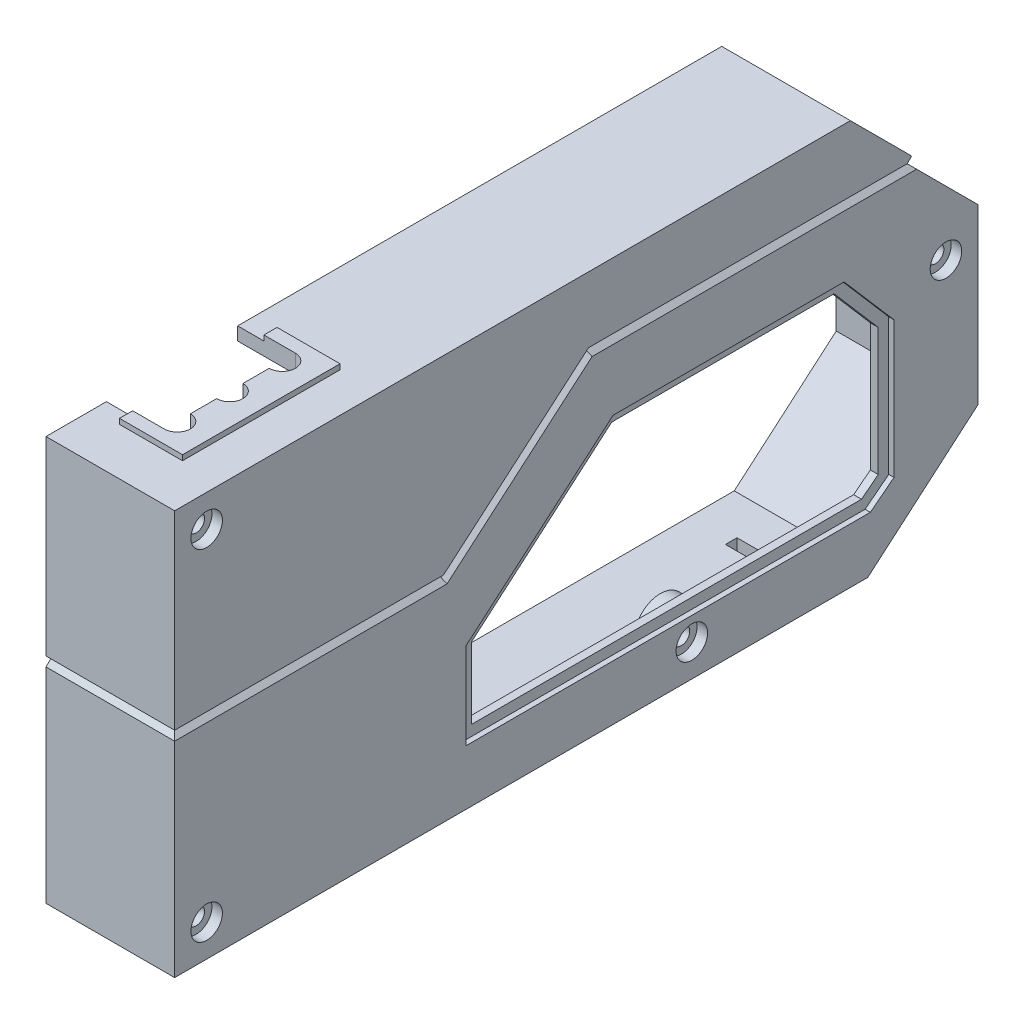
SolidWorks part; units mm, degrees
ref_plane "Front Plane" through (0, 0, 0) normal (0, 0, 1) x (1, 0, 0)
ref_plane "Top Plane" through (0, 0, 0) normal (0, 1, 0) x (1, 0, 0)
ref_plane "Right Plane" through (0, 0, 0) normal (1, 0, 0) x (0, 0, -1)
sketch "Sketch1" plane through (0, 0, 0) normal (1, 0, 0) x (0, 0, -1)
  line L0 (0, 0) -> (0, 77)
  line L1 (0, 77) -> (127, 77)
  line L2 (127, 77) -> (153, 51)
  line L3 (153, 51) -> (153, 18)
  line L4 (153, 18) -> (132, 0)
  line L5 (132, 0) -> (0, 0)
  dimension "D1" = 132
  dimension "D2" = 77
  dimension "D3" = 26
  dimension "D4" = 26
  dimension "D5" = 153
  dimension "D6" = 18
extrude "Base" add sketch "Sketch1" along normal blind 2.5
sketch "Sketch11" plane through (0, 0, 0) normal (-1, 0, 0) x (0, 0, 1)
  line L12 (-131.0752, 2.5) -> (-2.5, 2.5)
  line L13 (-2.5, 2.5) -> (-2.5, 74.5)
  line L14 (-2.5, 74.5) -> (-125.9645, 74.5)
  line L15 (-125.9645, 74.5) -> (-150.5, 49.9645)
  line L16 (-150.5, 49.9645) -> (-150.5, 19.1498)
  line L17 (-150.5, 19.1498) -> (-131.0752, 2.5)
  line L18 (-131.0752, 2.5) -> (-2.5, 2.5)
  line L19 (-2.5, 2.5) -> (-2.5, 74.5)
  line L20 (-2.5, 74.5) -> (-125.9645, 74.5)
  line L21 (-125.9645, 74.5) -> (-150.5, 49.9645)
  line L22 (-150.5, 49.9645) -> (-150.5, 19.1498)
  line L23 (-150.5, 19.1498) -> (-131.0752, 2.5)
  line M7 (-132, 0) -> (0, 0)
  line M8 (0, 0) -> (0, 77)
  line M9 (0, 77) -> (-127, 77)
  line M10 (-127, 77) -> (-153, 51)
  line M11 (-153, 51) -> (-153, 18)
  line M12 (-153, 18) -> (-132, 0)
  dimension "D1" = 2.5
extrude "Boss-Extrude6" add sketch "Sketch11" along normal blind 22 contours L23 L22 L21 L20 L19 L18 M12 M7 M8 M9 M10 M11 region at (0, 10.3005, -141.3853)
ref_plane "Middle" through (-11, 0, 0) normal (1, 0, 0) x (0, 0, -1)
sketch "Sketch17" plane through (0, 77, 0) normal (0, 1, 0) x (1, 0, 0)
  line L5 (-11, -42.35) -> (-11, 42.35) construction
  line L6 (-5, 39) -> (-17, 39)
  line L7 (-5, 39) -> (-5, 9)
  line L8 (-5, 9) -> (-17, 9)
  line L9 (-17, 39) -> (-17, 9)
  line L10 (-5, 39) -> (-17, 9) construction
  line L11 (-5, 9) -> (-17, 39) construction
  line L12 (2.5, 0) -> (-22, 0) construction
  point P0 (-11, 24)
  dimension "D1" = 12
  dimension "D2" = 30
  dimension "D3" = 24
extrude "Boss-Extrude8" add sketch "Sketch17" along normal blind 1
sketch "Sketch13" plane through (0, 78, 0) normal (0, 1, 0) x (1, 0, 0)
  line L0 (-22, 11.5) -> (-11, 11.5)
  line L1 (-22, 0) -> (-22, 127) construction
  line L2 (-11, 16.5) -> (-11, 21.5)
  line L3 (-11, 26.5) -> (-11, 31.5)
  line L4 (-11, 36.5) -> (-22, 36.5)
  line L5 (-22, 36.5) -> (-22, 11.5)
  line L6 (-5, 9) -> (-5, 39) construction
  line L7 (-11, -42.35) -> (-11, 42.35) construction
  arc A0 (-11, 11.5) -> (-11, 16.5) centre (-11, 14) ccw
  arc A1 (-11, 21.5) -> (-11, 26.5) centre (-11, 24) ccw
  arc A2 (-11, 31.5) -> (-11, 36.5) centre (-11, 34) ccw
  point P9 (-5, 24)
  dimension "D1" = 5
  dimension "D4" = 10
  dimension "D5" = 10
extrude "Cut-Extrude2" cut sketch "Sketch13" against normal up to next
sketch "Sketch19" plane through (2.5, 0, 0) normal (1, 0, 0) x (0, 0, -1)
  line L0 (127, 77) -> (128.6971, 77)
  line L1 (128.6971, 77) -> (140.3643, 65.3327)
  line L2 (140.3643, 65.3327) -> (139.5158, 64.4842)
  line L3 (153, 51) -> (127, 77) construction
  line L4 (139.5158, 64.4842) -> (127, 77)
  dimension "D1" = 1.2
  dimension "D2" = 16.5
extrude "Boss-Extrude9" add sketch "Sketch19" against normal up to vertex (24.5 mm away) up to point (-22, 77, -127)
sketch "Sketch20" plane through (0, 102.8485, -102.8485) normal (0, 0.7071, -0.7071) x (-1, 0, 0)
  line L1 (11, 42.35) -> (11, -42.35) construction
  line L2 (2.5, -53.0553) -> (19.5, -53.0553)
  line L3 (2.5, -53.0553) -> (2.5, -44.5553)
  line L4 (2.5, -44.5553) -> (19.5, -44.5553)
  line L5 (19.5, -53.0553) -> (19.5, -44.5553)
  line L6 (2.5, -53.0553) -> (19.5, -44.5553) construction
  line L7 (2.5, -44.5553) -> (19.5, -53.0553) construction
  line L8 (-2.5, -53.0553) -> (-2.5, -36.5553) construction
  line L9 (22, -36.5553) -> (-2.5, -36.5553) construction
  line L10 (22, -53.0553) -> (-2.5, -53.0553) construction
  point P2 (11, -48.8053)
  dimension "D1" = 5
  dimension "D2" = 8
extrude "Cut-Extrude5" cut sketch "Sketch20" against normal up to vertex (1.2 mm away) up to point (2.5, 64.4842, -139.5158)
sketch "Sketch21" plane through (0, 102, -102) normal (0, 0.7071, -0.7071) x (-1, 0, 0)
  line L0 (11, 48.4) -> (11, -48.4) construction
  line L1 (19.5, -44.5553) -> (2.5, -44.5553) construction
  line L2 (11, -48.0053) -> (22, -48.0053)
  line L3 (22, -48.0053) -> (22, -53.1053)
  line L4 (22, -53.0553) -> (22, -72.1249) construction
  line L5 (11, -53.1053) -> (22, -53.1053)
  line L6 (22, 44.5477) -> (22, 46.3155) construction
  arc A0 (11, -48.0053) -> (11, -53.1053) centre (11, -50.5553) ccw
  dimension "D1" = 5.1
  dimension "D2" = 6
extrude "Cut-Extrude6" cut sketch "Sketch21" against normal mid plane 10
sketch "Sketch28" plane through (2.5, 0, 0) normal (1, 0, 0) x (0, 0, -1)
  circle A0 centre (6.1, 70.9) radius 5
  circle A1 centre (146.9, 44.9) radius 5
  circle A2 centre (98.5, 6.1) radius 5
  circle A3 centre (6.1, 6.1) radius 5
  dimension "D9" = 10
  dimension "D1" = 6.1
  dimension "D2" = 6.1
  dimension "D3" = 70.9
  dimension "D4" = 6.1
  dimension "D5" = 98.5
  dimension "D6" = 6.1
  dimension "D7" = 44.9
  dimension "D8" = 146.9
extrude "Boss-Extrude11" add sketch "Sketch28" against normal blind 6
sketch "Sketch29" plane through (2.5, 0, 0) normal (1, 0, 0) x (0, 0, -1)
  circle A0 centre (6.1, 70.9) radius 3
  circle A1 centre (146.9, 44.9) radius 3
  circle A2 centre (98.5, 6.1) radius 3
  circle A3 centre (6.1, 6.1) radius 3
  dimension "D1" = 6
extrude "Cut-Extrude11" cut sketch "Sketch29" against normal blind 2
sketch "Sketch30" plane through (0.5, 0, 0) normal (1, 0, 0) x (0, 0, -1)
  circle A0 centre (6.1, 70.9) radius 1.6
  circle A1 centre (6.1, 6.1) radius 1.6
  circle A2 centre (146.9, 44.9) radius 1.6
  circle A3 centre (98.5, 6.1) radius 1.6
  dimension "D1" = 3.2
extrude "Cut-Extrude12" cut sketch "Sketch30" against normal up to next
sketch "Sketch31" plane through (0, 0, 0) normal (-1, 0, 0) x (0, 0, 1)
  line L1 (-14.5, 47.5) -> (-4.5, 47.5)
  line L2 (-14.5, 47.5) -> (-14.5, 22.5)
  line L3 (-14.5, 22.5) -> (-4.5, 22.5)
  line L4 (-4.5, 47.5) -> (-4.5, 22.5)
  line L5 (-14.5, 47.5) -> (-4.5, 22.5) construction
  line L6 (-14.5, 22.5) -> (-4.5, 47.5) construction
  point P0 (-9.5, 35)
  dimension "D1" = 9.5
  dimension "D2" = 35
  dimension "D3" = 25
  dimension "D4" = 10
extrude "Battery_Support" add sketch "Sketch31" along normal blind 3.4
sketch "Sketch25" plane through (2.5, 0, 0) normal (1, 0, 0) x (0, 0, -1)
  line L0 (55.5, 10.5) -> (132.5, 10.5)
  line L1 (132.5, 10.5) -> (137, 14)
  line L2 (137, 14) -> (137, 40)
  line L3 (137, 40) -> (127.5, 51)
  line L4 (127.5, 51) -> (83.5, 51)
  line L5 (83.5, 51) -> (55.5, 27)
  line L6 (55.5, 27) -> (55.5, 10.5)
  dimension "D1" = 77
  dimension "D2" = 4.5
  dimension "D3" = 3.5
  dimension "D4" = 72
  dimension "D5" = 26
  dimension "D6" = 10.5
  dimension "D7" = 55.5
  dimension "D8" = 40.5
  dimension "D9" = 28
  dimension "D10" = 16.5
extrude "Cut-Extrude9" cut sketch "Sketch25" against normal blind 1
sketch "Sketch26" plane through (1.5, 0, 0) normal (1, 0, 0) x (0, 0, -1)
  line L14 (57.5, 26.0801) -> (57.5, 12.5)
  line L15 (57.5, 12.5) -> (131.8138, 12.5)
  line L16 (131.8138, 12.5) -> (135, 14.9782)
  line L17 (135, 14.9782) -> (135, 39.2559)
  line L18 (135, 39.2559) -> (126.5846, 49)
  line L19 (126.5846, 49) -> (84.2398, 49)
  line L20 (84.2398, 49) -> (57.5, 26.0801)
  line L21 (57.5, 26.0801) -> (57.5, 12.5)
  line L22 (57.5, 12.5) -> (131.8138, 12.5)
  line L23 (131.8138, 12.5) -> (135, 14.9782)
  line L24 (135, 14.9782) -> (135, 39.2559)
  line L25 (135, 39.2559) -> (126.5846, 49)
  line L26 (126.5846, 49) -> (84.2398, 49)
  line L27 (84.2398, 49) -> (57.5, 26.0801)
  dimension "D1" = 2
extrude "Cut-Extrude10" cut sketch "Sketch26" against normal up to next
sketch "Sketch32" plane through (2.5, 0, 0) normal (1, 0, 0) x (0, 0, -1)
  line L0 (144.5158, 63.6842) -> (79.1216, 63.6842)
  line L1 (79.1216, 63.6842) -> (51.49, 40)
  line L2 (51.49, 40) -> (0, 40)
  line L3 (0, 77) -> (0, 0) construction
  line L4 (83.5, 51) -> (55.5, 27) construction
  line L5 (144.5158, 63.6842) -> (144.5158, 64.4842)
  line L6 (144.5158, 64.4842) -> (78.8257, 64.4842)
  line L7 (78.8257, 64.4842) -> (51.1941, 40.8)
  line L8 (51.1941, 40.8) -> (0, 40.8)
  line L9 (0, 40.8) -> (0, 40)
  dimension "D1" = 0.8
  dimension "D2" = 0.8
  dimension "D3" = 0.8
  dimension "D4" = 5
  dimension "D5" = 12.48
  dimension "D6" = 40
extrude "Cut-Extrude13" cut sketch "Sketch32" against normal blind 1
sketch "Sketch33" plane through (0, 0, 0) normal (0, 0, 1) x (1, 0, 0)
  line L0 (-22, 0) -> (-22, 77) construction
  line L1 (1.5, 40.8) -> (-22, 40.8)
  line L2 (1.5, 40.8) -> (1.5, 40)
  line L3 (1.5, 40) -> (-22, 40)
  line L4 (-22, 40.8) -> (-22, 40)
  point P7 (1.5, 40)
extrude "Cut-Extrude14" cut sketch "Sketch33" against normal blind 1
chamfer "Chamfer1" distance 1 angle 45 4 edges at (-9.75, 40, 0) (2.5, 40, -25.745) (2.5, 51.8421, -65.3058) (2.5, 63.6842, -109.7187)
sketch "Sketch23" plane through (0, 0, 0) normal (0, -1, 0) x (1, 0, 0)
  line L0 (-11, -42.9) -> (-11, 42.9) construction
  line L2 (-8, -10.5) -> (-14, -10.5)
  line L3 (-8, -10.5) -> (-8, -8.3)
  line L4 (-8, -123.6) -> (-14, -123.6)
  line L5 (-5.5, -10.5) -> (-16.5, -10.5)
  line L6 (-5.5, -10.5) -> (-5.5, -60.5)
  line L7 (-5.5, -60.5) -> (-16.5, -60.5)
  line L8 (-16.5, -10.5) -> (-16.5, -60.5)
  line L9 (-8, -123.6) -> (-8, -121.4)
  line L10 (-8, -121.4) -> (-14, -121.4)
  line L11 (-8, -8.3) -> (-14, -8.3)
  line L12 (-14, -10.5) -> (-14, -8.3)
  line L13 (-8, -10.5) -> (-14, -8.3) construction
  line L14 (-8, -8.3) -> (-14, -10.5) construction
  line L15 (-14, -123.6) -> (-14, -121.4)
  line L16 (-8, -123.6) -> (-14, -121.4) construction
  line L17 (-8, -121.4) -> (-14, -123.6) construction
  point P4 (-11, -10.5)
  point P7 (-11, -9.4)
  point P13 (0, 0)
  point P15 (-11, -122.5)
  dimension "D1" = 10.5
  dimension "D2" = 11
  dimension "D3" = 6
  dimension "D4" = 50
  dimension "D5" = 2.2
  dimension "D6" = 6
  dimension "D7" = 2.2
  dimension "D8" = 122.5
extrude "Cut-Extrude7" cut sketch "Sketch23" against normal up to next contours L5 L8 L7 L6 L2 | L12 L2 L3 L11 | L15 L4 L9 L10 region at (-11, 0, -35.5) region at (-11, 0, -9.4) region at (-11, 0, -122.5)
equation "\"D5@Sketch13\"=\"D4@Sketch13\""
equation "\"D2@Sketch32\"=\"D1@Sketch32\""
equation "\"D3@Sketch32\"=\"D1@Sketch32\""
